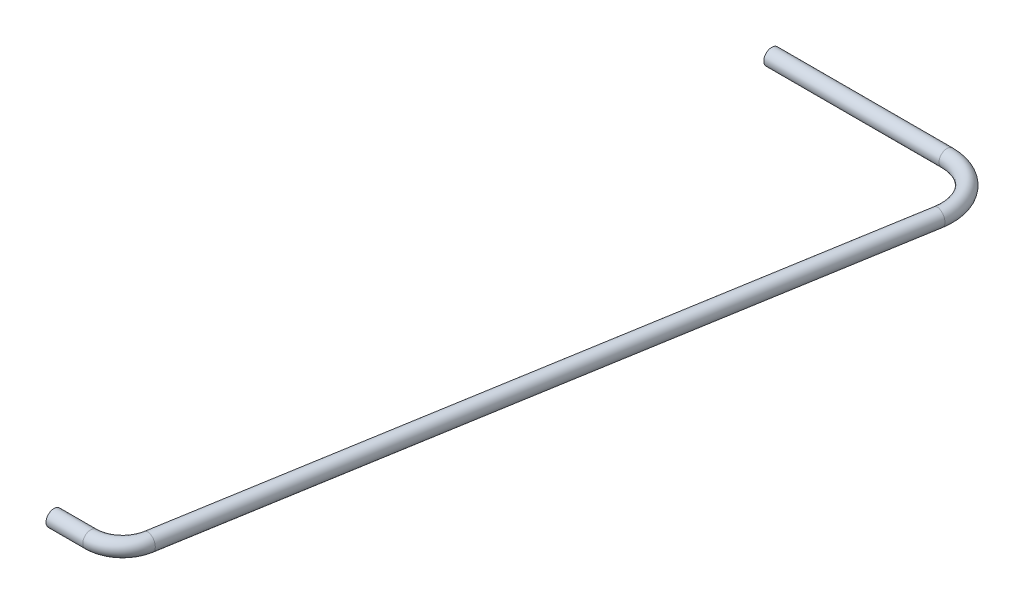
SolidWorks part; units mm, degrees
ref_plane "Front Plane" through (0, 0, 0) normal (0, 0, 1) x (1, 0, 0)
ref_plane "Top Plane" through (0, 0, 0) normal (0, 1, 0) x (1, 0, 0)
ref_plane "Right Plane" through (0, 0, 0) normal (1, 0, 0) x (0, 0, -1)
sketch "Sketch1" plane through (0, 0, 0) normal (0, 1, 0) x (1, 0, 0)
  line L1 (-5, 0) -> (6.5408, 0)
  line L2 (16.4024, 8.3421) -> (52.0602, 220.4467)
  line L3 (37.2678, 237.9335) -> (-17.7322, 237.9335)
  arc A0 (52.0602, 220.4467) -> (37.2678, 237.9335) centre (37.2678, 222.9335) ccw
  arc A1 (16.4024, 8.3421) -> (6.5408, 0) centre (6.5408, 10) cw
  point P3 (0, 0)
  point P9 (0, 0)
  point P10 (15.5046, 0)
  point P11 (15, 0)
  dimension "D1" = 15
  dimension "D2" = 20
  dimension "D3" = 10
  dimension "D4" = 55
sweep "Sweep1" add path "Sketch1" circular profile diameter 5 parameters "D3"=5
